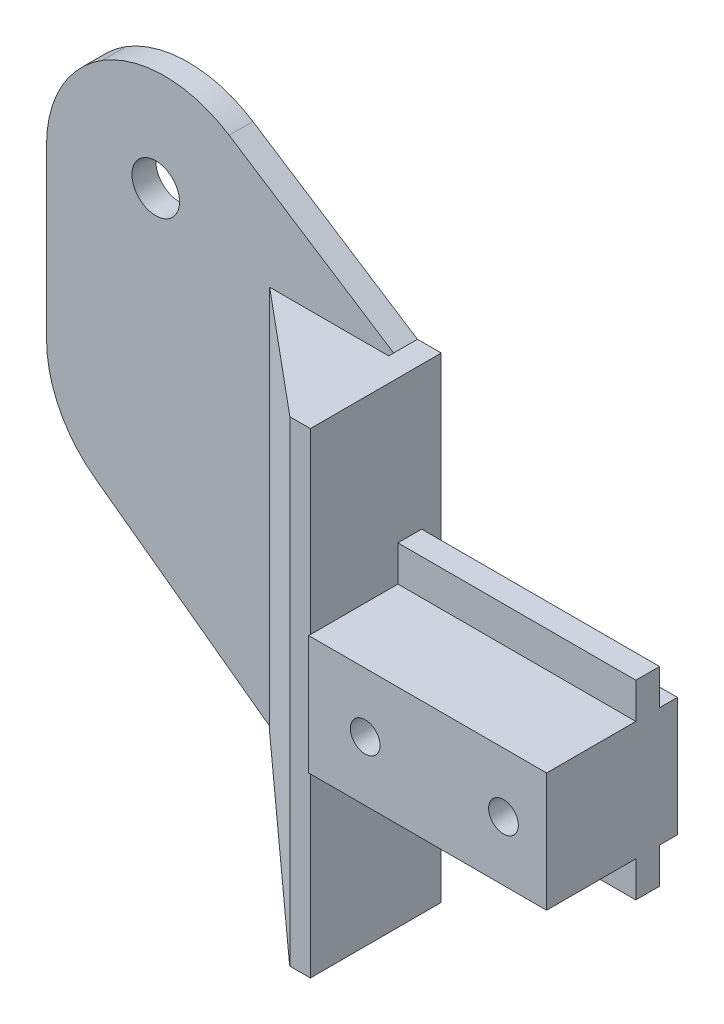
SolidWorks part; units mm, degrees
ref_plane "Front Plane" through (0, 0, 0) normal (0, 0, 1) x (1, 0, 0)
ref_plane "Top Plane" through (0, 0, 0) normal (0, 1, 0) x (1, 0, 0)
ref_plane "Right Plane" through (0, 0, 0) normal (1, 0, 0) x (0, 0, -1)
sketch "Sketch1" plane through (0, 0, 0) normal (0, 0, 1) x (1, 0, 0)
  line L1 (10, 5) -> (-10, 5)
  line L2 (10, 5) -> (10, -5)
  line L3 (10, -5) -> (-10, -5)
  line L4 (-10, 5) -> (-10, -5)
  line L5 (0, -5) -> (0, 5) construction
  line L6 (10, 0) -> (-10, 0) construction
  point P0 (0, 0)
  dimension "D1" = 10
  dimension "D2" = 20
extrude "Boss-Extrude1" add sketch "Sketch1" along normal blind 11
sketch "Sketch2" plane through (0, 5, 0) normal (0, 1, 0) x (1, 0, 0)
  line L0 (10, -11) -> (10, 0) construction
  line L1 (-10, -1.5) -> (10, -1.5)
  line L2 (-10, -1.5) -> (-10, -3.5)
  line L3 (-10, -3.5) -> (10, -3.5)
  line L4 (10, -1.5) -> (10, -3.5)
  line L5 (0, -3.5) -> (0, -1.5) construction
  line L6 (-10, -2.5) -> (10, -2.5) construction
  line L7 (10, -11) -> (-10, -11) construction
  point P0 (0, -2.5)
  dimension "D1" = 20
  dimension "D2" = 2
  dimension "D3" = 7.5
extrude "Boss-Extrude2" add sketch "Sketch2" along normal blind 3 and the other way blind 13
sketch "Sketch3" plane through (-10, 0, 0) normal (-1, 0, 0) x (0, 0, 1)
  line L1 (10.8575, 20) -> (-0.1425, 20)
  line L2 (10.8575, 20) -> (10.8575, -20)
  line L3 (10.8575, -20) -> (-0.1425, -20)
  line L4 (-0.1425, 20) -> (-0.1425, -20)
  line L5 (5.3575, -20) -> (5.3575, 20) construction
  line L6 (10.8575, 0) -> (-0.1425, 0) construction
  point P0 (5.3575, 0)
  dimension "D1" = 40
  dimension "D2" = 11
extrude "Boss-Extrude3" add sketch "Sketch3" along normal blind 2
sketch "Sketch5" plane through (-12, 0, 0) normal (-1, 0, 0) x (0, 0, 1)
  line L0 (-0.1425, 20) -> (-0.1425, -20) construction
  line L1 (1.8575, -20) -> (-0.1425, -20)
  line L2 (1.8575, -20) -> (1.8575, 40)
  line L3 (1.8575, 40) -> (-0.1425, 40)
  line L4 (-0.1425, -20) -> (-0.1425, 40)
  line L5 (0.8575, 40) -> (0.8575, -20) construction
  line L6 (1.8575, 10) -> (-0.1425, 10) construction
  line L7 (-0.1425, -20) -> (10.8575, -20) construction
  point P0 (0.8575, 10)
  dimension "D1" = 60
  dimension "D2" = 2
  dimension "D3" = 0
  dimension "D4" = 0
extrude "Boss-Extrude4" add sketch "Sketch5" along normal blind 40
hole_wizard "Ø4.0mm Dowel Slot1" positions "Sketch6" profile "Sketch7" size "Ø4.0" standard "ANSI Metric" slot yes end condition through all
sketch "Sketch6" plane through (0, 0, -0.1425) normal (0, 0, -1) x (-1, 0, 0)
  line L0 (52, 40) -> (12, 40) construction
  line L1 (12, 40) -> (12, 20) construction
  point P0 (32, 22)
  dimension "D1" = 18
  dimension "D2" = 20
sketch "Sketch7" plane through (-32, 22, -0.1425) normal (1, 0, 0) x (0, 1, 0)
  line L0 (0, 0) -> (0, 11.1425)
  line L1 (0, 11.1425) -> (2, 11.1425)
  line L2 (2, 11.1425) -> (2, 0)
  line L5 (2, 0) -> (0, 0)
  line L11 (0, -6.35) -> (0, 107.95) construction
  dimension "Thru Hole Dia." = 4
  dimension "Thru Hole Depth" = 11.1425
sketch "Sketch9" plane through (0, 0, -0.1425) normal (0, 0, -1) x (-1, 0, 0)
  line L0 (12, 20) -> (31.1137, 32.3552)
  line L1 (31.1137, 32.3552) -> (52, 19.5788)
  line L2 (52, 40) -> (52, -20) construction
  line L3 (52, 19.5788) -> (52, 40)
  line L4 (52, 40) -> (12, 40)
  line L5 (12, 40) -> (12, 20)
extrude "Cut-Extrude1" cut sketch "Sketch9" against normal blind 40
sketch "Sketch10" plane through (0, 0, 1.8575) normal (0, 0, 1) x (1, 0, 0)
  line L0 (-12, -20) -> (-52, 9.2235)
  line L1 (-52, -20) -> (-52, 19.5788) construction
  line L2 (-52, 9.2235) -> (-52, -20)
  line L3 (-52, -20) -> (-12, -20)
extrude "Cut-Extrude2" cut sketch "Sketch10" against normal blind 40
fillet "Fillet1" radius 10 3 edges at (-31.1137, 32.3552, 0.8575) (-52, 19.5788, 0.8575) (-52, 9.2235, 0.8575)
sketch "Sketch11" plane through (0, 0, 1.8575) normal (0, 0, 1) x (1, 0, 0)
  line L1 (-94.8108, 98.757) -> (-41.179, 98.757)
  line L2 (-94.8108, 98.757) -> (-94.8108, -19.9992)
  line L3 (-94.8108, -19.9992) -> (-41.179, -19.9992)
  line L4 (-41.179, 98.757) -> (-41.179, -19.9992)
  line L5 (-67.9949, -19.9992) -> (-67.9949, 98.757) construction
  line L6 (-94.8108, 39.3789) -> (-41.179, 39.3789) construction
  point P0 (-67.9949, 39.3789)
extrude "Cut-Extrude3" cut sketch "Sketch11" against normal blind 40
fillet "Fillet2" radius 10 2 edges at (-41.179, 1.3178, 0.8575) (-41.179, 26.1982, 0.8575)
sketch "Sketch12" plane through (-12, 0, 0) normal (-1, 0, 0) x (0, 0, 1)
  line L1 (2.2779, 20) -> (10.8575, 20)
  line L2 (2.2779, 20) -> (2.2779, -20)
  line L3 (2.2779, -20) -> (10.8575, -20)
  line L4 (10.8575, 20) -> (10.8575, -20)
  line L5 (6.5677, -20) -> (6.5677, 20) construction
  line L6 (2.2779, 0) -> (10.8575, 0) construction
  point P0 (6.5677, 0)
extrude "Boss-Extrude5" add sketch "Sketch12" along normal blind 10
sketch "Sketch13" plane through (0, -20, 0) normal (0, -1, 0) x (1, 0, 0)
  line L0 (-22, 2.2779) -> (-11.7252, 10.8575)
  line L1 (-22, 10.8575) -> (-10, 10.8575) construction
  line L2 (-11.7252, 10.8575) -> (-22, 10.8575)
  line L3 (-22, 10.8575) -> (-22, 2.2779)
extrude "Cut-Extrude4" cut sketch "Sketch13" against normal blind 40
sketch "Sketch14" plane through (0, 0, 2.2779) normal (0, 0, -1) x (-1, 0, 0)
  line L0 (12.5876, -20) -> (22, -12.6924)
  line L1 (22, -20) -> (12, -20) construction
  line L2 (22, 20) -> (22, -20) construction
  line L3 (22, -12.6924) -> (22, -14.379)
  line L4 (22, -14.379) -> (22, -18.9487)
  line L5 (22, -20) -> (12.5876, -20)
sketch "Sketch15" plane through (0, 0, 2.2779) normal (0, 0, -1) x (-1, 0, 0)
  line L0 (22, -20) -> (11.907, -20)
  line L1 (11.907, -20) -> (22, -12.4615)
  line L2 (22, -12.4615) -> (22, -20)
extrude "Cut-Extrude5" cut sketch "Sketch15" against normal blind 40
hole_wizard "Ø2.5mm Dowel Slot1" positions "Sketch16" profile "Sketch17" size "Ø2.5" standard "ANSI Metric" slot yes end condition through all
sketch "Sketch16" plane through (0, 0, 11) normal (0, 0, 1) x (1, 0, 0)
  point P0 (-5.2507, 0)
  point P2 (6.3741, 0)
sketch "Sketch17" plane through (-5.2507, 0, 11) normal (1, 0, 0) x (0, -1, 0)
  line L0 (0, 0) -> (0, 11.1425)
  line L1 (0, 11.1425) -> (1.25, 11.1425)
  line L2 (1.25, 11.1425) -> (1.25, 0)
  line L5 (1.25, 0) -> (0, 0)
  line L11 (0, -6.35) -> (0, 107.95) construction
  dimension "Thru Hole Dia." = 2.5
  dimension "Thru Hole Depth" = 11.1425
